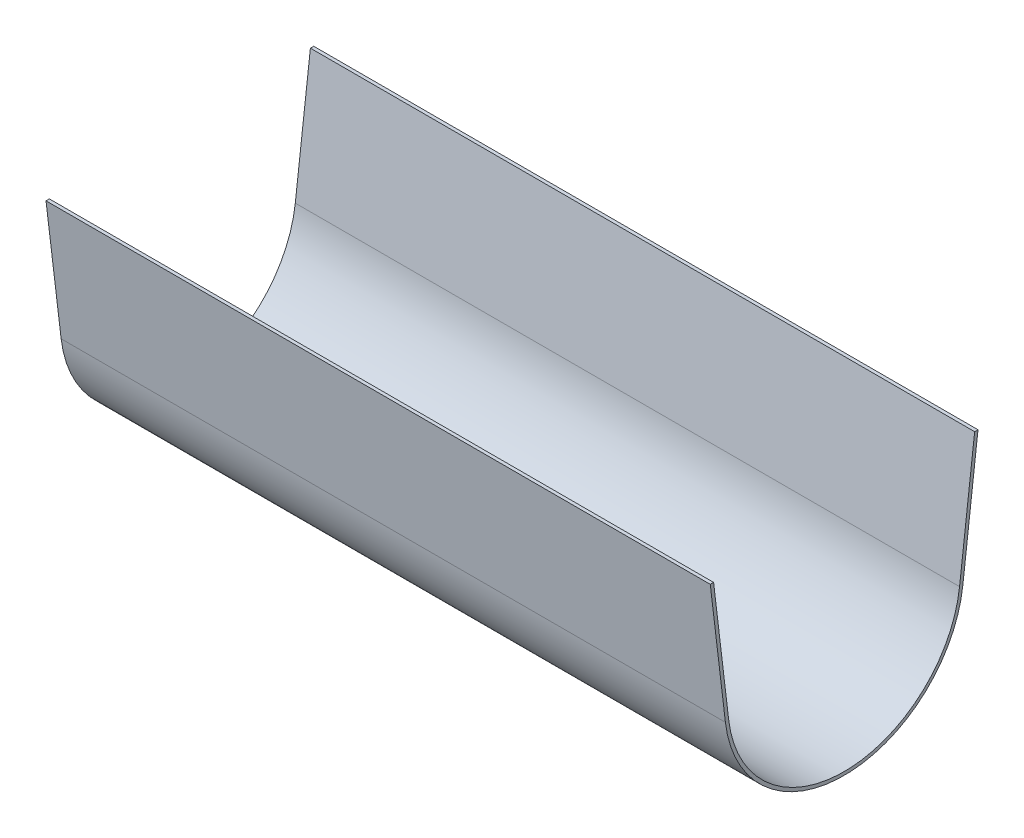
SolidWorks part; units mm, degrees
material "Silicon Rubber"
ref_plane "Front Plane" through (0, 0, 0) normal (0, 0, 1) x (1, 0, 0)
ref_plane "Top Plane" through (0, 0, 0) normal (0, 1, 0) x (1, 0, 0)
ref_plane "Right Plane" through (0, 0, 0) normal (1, 0, 0) x (0, 0, -1)
sketch "Sketch1" plane through (0, 0, 0) normal (1, 0, 0) x (0, 0, -1)
  line L0 (0, 0) -> (50000, 0) construction
  line L3 (-40.305, 0) -> (-35.7472, -38.2586)
  line L4 (40.305, 0) -> (35.7472, -38.2586)
  line L5 (-39.2979, 0) -> (-34.7543, -38.1403)
  line L6 (39.2979, 0) -> (34.7543, -38.1403)
  line L7 (-40.305, 0) -> (-39.2979, 0)
  line L8 (-39.312, 0.1183) -> (-34.7543, -38.1403) construction
  line L9 (40.305, 0) -> (39.2979, 0)
  line L10 (39.312, 0.1183) -> (34.7543, -38.1403) construction
  arc A0 (-35.7472, -38.2586) -> (35.7472, -38.2586) centre (0, -34) ccw
  arc A1 (-34.7543, -38.1403) -> (34.7543, -38.1403) centre (0, -34) ccw
  point P0 (0, -70)
  dimension "D4" = 70
  dimension "D3" = 35
  dimension "D2" = 80.61
  dimension "D1" = 1
extrude "Boss-Extrude1" add sketch "Sketch1" along normal mid plane 200
sketch "Sketch2" plane through (100, 0, 0) normal (1, 0, 0) x (0, 0, -1)
  line L0 (0, -34) -> (0, 255.3768)
  point P0 (0, -34)
